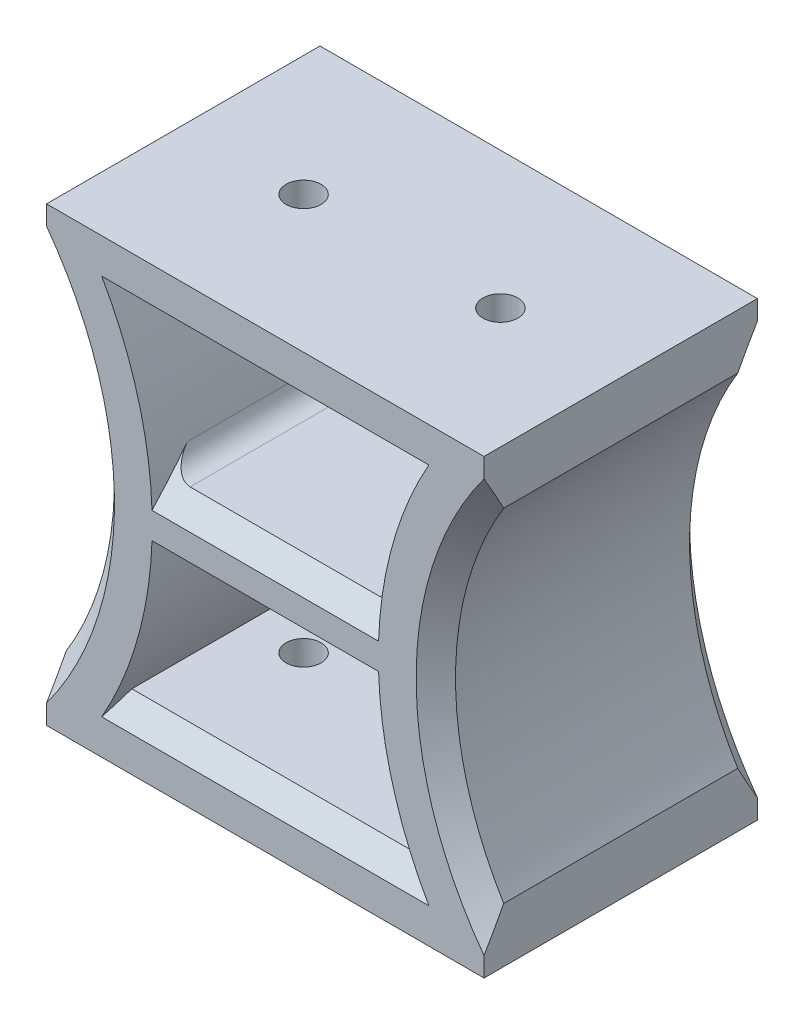
SolidWorks part; units mm, degrees
ref_plane "Plan de face" through (0, 0, 0) normal (0, 0, 1) x (1, 0, 0)
ref_plane "Plan de dessus" through (0, 0, 0) normal (0, 1, 0) x (1, 0, 0)
ref_plane "Plan de droite" through (0, 0, 0) normal (1, 0, 0) x (0, 0, -1)
sketch "Esquisse1" plane through (0, 0, 0) normal (0, 0, 1) x (1, 0, 0)
  line L1 (-20, 20.65) -> (20, 20.65)
  line L2 (-20, 20.65) -> (-20, -20.65)
  line L3 (-20, -20.65) -> (20, -20.65)
  line L4 (20, 20.65) -> (20, -20.65)
  point P4 (0, 20.65)
  point P7 (20, 0)
  dimension "D1" = 40
  dimension "D2" = 41.3
extrude "Boss.-Extru.1" add sketch "Esquisse1" along normal blind 12.5 and the other way blind 12.5
sketch "Esquisse2" plane through (0, 0, 12.5) normal (0, 0, 1) x (1, 0, 0)
  line L0 (-20, 0) -> (20, 0) construction
  line L1 (-20, 20.65) -> (-20, -20.65) construction
  line L2 (20, -20.65) -> (20, 20.65) construction
  line L3 (-20, -20.65) -> (20, -20.65) construction
  line L4 (20, 20.65) -> (-20, 20.65) construction
  line L5 (-20, 15.65) -> (-20, -15.65)
  line L6 (0, 20.65) -> (0, -20.65) construction
  line L7 (20, 15.65) -> (20, -15.65)
  line L8 (-14, -15.65) -> (14, -15.65)
  line L9 (-10.4642, -3) -> (10.4642, -3)
  line L20 (-14, 15.65) -> (14, 15.65)
  line L21 (-10.4642, 3) -> (10.4642, 3)
  arc A0 (-20, 15.65) -> (-20, -15.65) centre (-45.5945, 0) cw
  arc A1 (20, 15.65) -> (20, -15.65) centre (45.5945, 0) ccw
  arc A3 (-14, -15.65) -> (-10.4642, -3) centre (-45.5945, 0) ccw
  arc A4 (14, -15.65) -> (10.4642, -3) centre (45.5945, 0) cw
  arc A7 (14, 15.65) -> (10.4642, 3) centre (45.5945, 0) ccw
  arc A8 (-14, 15.65) -> (-10.4642, 3) centre (-45.5945, 0) cw
  dimension "D1" = 5
  dimension "D3" = 30
  dimension "D2" = 5
  dimension "D4" = 6
  dimension "D5" = 5
  dimension "D6" = 3
extrude "Enlèv. mat.-Extru.1" cut sketch "Esquisse2" against normal up to next
sketch "Esquisse3" plane through (0, 20.65, 0) normal (0, 1, 0) x (1, 0, 0)
  line L0 (-20, 0) -> (20, 0) construction
  line L1 (-20, 12.5) -> (-20, -12.5) construction
  line L2 (20, 12.5) -> (20, -12.5) construction
  circle A0 centre (-9, 0) radius 1.6
  circle A1 centre (9, 0) radius 1.6
  dimension "D1" = 3.2
  dimension "D2" = 3.2
  dimension "D3" = 9
  dimension "D4" = 9
extrude "Enlèv. mat.-Extru.2" cut sketch "Esquisse3" against normal up to next
sketch "Esquisse4" plane through (0, -20.65, 0) normal (0, -1, 0) x (1, 0, 0)
  line L0 (-20, 0) -> (20, 0) construction
  line L1 (-20, -12.5) -> (-20, 12.5) construction
  line L2 (20, -12.5) -> (20, 12.5) construction
  circle A0 centre (-9, 0) radius 1.6
  circle A1 centre (9, 0) radius 1.6
  dimension "D1" = 3.2
  dimension "D2" = 3.2
  dimension "D3" = 9
  dimension "D4" = 9
extrude "Enlèv. mat.-Extru.3" cut sketch "Esquisse4" against normal up to next
sketch "Esquisse7" plane through (0, 0, 0) normal (1, 0, 0) x (0, 0, -1)
  line L3 (-12.5, 15.65) -> (-12.5, 20.65) construction
  line L4 (-12.5, -20.65) -> (-12.5, -15.65) construction
  line L5 (12.5, 20.65) -> (-12.5, 20.65) construction
  line L6 (12.5, -20.65) -> (-12.5, -20.65) construction
  line L7 (-12.5, 17.65) -> (-12.5, -17.65)
  line L8 (0, 30.8287) -> (0, -33.283) construction
  line L9 (12.5, 17.65) -> (12.5, -17.65)
  arc A0 (-12.5, 17.65) -> (-12.5, -17.65) centre (-34.2365, 0) cw
  arc A1 (12.5, 17.65) -> (12.5, -17.65) centre (34.2365, 0) ccw
  dimension "D3" = 28
  dimension "D1" = 3
  dimension "D2" = 3
extrude "Enlèv. mat.-Extru.5" [suppressed] cut sketch "Esquisse7" against normal blind 27.5 and the other way blind 27.5
chamfer "Chanfrein6" [suppressed] distance 1.8 angle 45
chamfer "Chanfrein7" distance 1.8 angle 45 12 edges at (-15.5945, 0, -12.5) (15.5945, 0, -12.5) (15.5945, 0, 12.5) (-15.5945, 0, 12.5) (0, -3, -12.5) (0, 3, -12.5) (0, -3, 12.5) (0, 3, 12.5) (0, 15.65, 12.5) (0, -15.65, 12.5) (0, -15.65, -12.5) (0, 15.65, -12.5)
fillet "Congé4" radius 2 4 edges at (10.4642, 3, 0) (-10.4642, 3, 0) (10.4642, -3, 0) (-10.4642, -3, 0)
